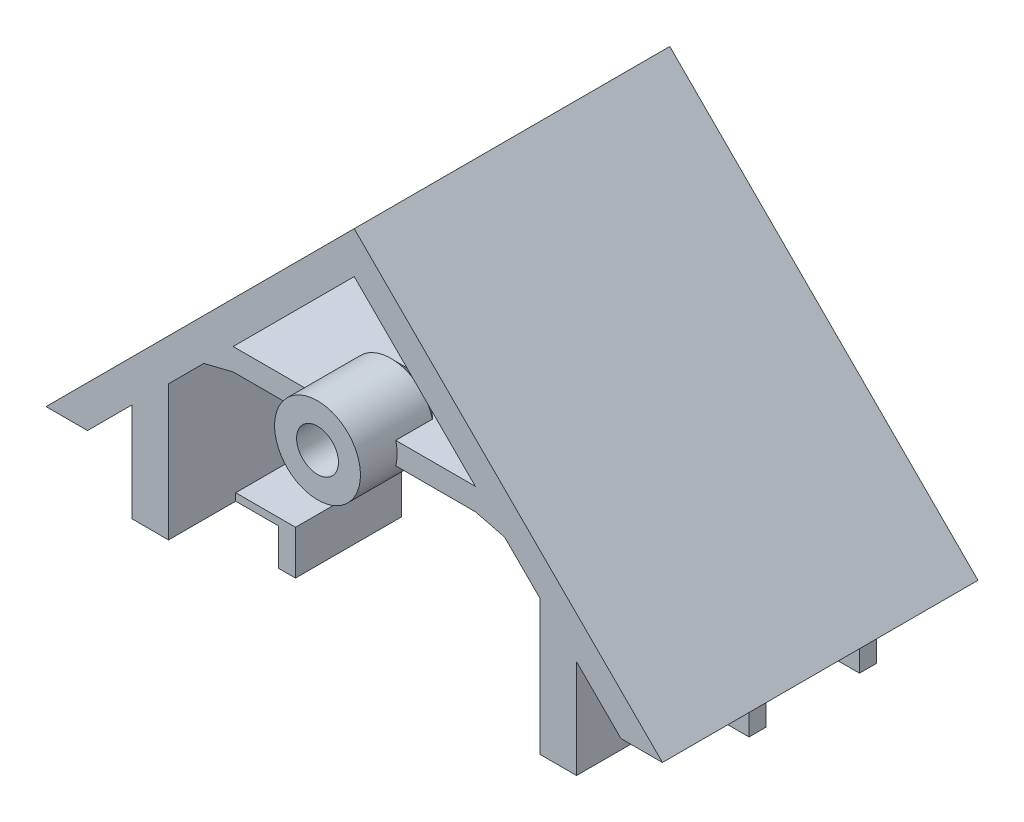
SolidWorks part; units mm, degrees
ref_plane "Front Plane" through (0, 0, 0) normal (0, 0, 1) x (1, 0, 0)
ref_plane "Top Plane" through (0, 0, 0) normal (0, 1, 0) x (1, 0, 0)
ref_plane "Right Plane" through (0, 0, 0) normal (1, 0, 0) x (0, 0, -1)
sketch "Sketch1" plane through (0, 0, 0) normal (0, 0, 1) x (1, 0, 0)
  line L1 (0, 0) -> (-42, -42)
  line L2 (0, -1000.3549) -> (0, 48999.6451) construction
  line L3 (-32.3431, -38) -> (-20.5, -26.1569)
  line L4 (32.3431, -38) -> (20.5, -26.1569)
  line L5 (0, 0) -> (42, -42)
  line L7 (-42, -42) -> (-16.5, -42) construction
  line L8 (-32.3431, -38) -> (-20.5, -38) construction
  line L9 (-34, -34) -> (34, -34) construction
  line L10 (-16.5, -42) -> (-16.5, -25.1569) construction
  line L11 (16.5, -42) -> (16.5, -25.1569) construction
  line L12 (16.5, -42) -> (42, -42) construction
  line L13 (20.5, -38) -> (32.3431, -38) construction
  line L14 (-20.5, -38) -> (-20.5, -26.1569) construction
  line L15 (20.5, -38) -> (20.5, -26.1569) construction
  line L16 (-16.5, -22.1569) -> (0, -5.6569)
  line L17 (16.5, -22.1569) -> (0, -5.6569)
  line L18 (16.5, -22.1569) -> (-16.5, -22.1569)
  line L19 (16.5, -25.1569) -> (-16.5, -25.1569)
  line L20 (-32.3431, -38) -> (-36.3431, -42)
  line L21 (-16.5, -25.1569) -> (-20.5, -26.1569)
  line L22 (16.5, -25.1569) -> (20.5, -26.1569)
  line L23 (32.3431, -38) -> (36.3431, -42)
  line L24 (-36.3431, -42) -> (-42, -42)
  line L25 (36.3431, -42) -> (42, -42)
  point P21 (0, -25.1569)
  dimension "D1" = 90
  dimension "D2" = 4
  dimension "D3" = 4
  dimension "D4" = 68
  dimension "D5" = 8
  dimension "D6" = 33
  dimension "D7" = 4
  dimension "D8" = 3
extrude "Boss-Extrude1" add sketch "Sketch1" along normal mid plane 43
sketch "Sketch11" plane through (0, 0, 21.5) normal (0, 0, 1) x (1, 0, 0)
  line L0 (0, -22.1569) -> (0, -25.1569) construction
  line L1 (-16.5, -22.1569) -> (16.5, -22.1569) construction
  line L2 (-16.5, -25.1569) -> (16.5, -25.1569) construction
  circle A0 centre (0, -23.6569) radius 5.85
  circle A1 centre (0, -23.6569) radius 2.85 construction
  point P8 (0, -23.6569)
  dimension "D1" = 5.7
  dimension "D2" = 3
extrude "Boss-Extrude7" add sketch "Sketch11" against normal blind 10 from offset 5
sketch "Sketch12" plane through (0, 0, 26.5) normal (0, 0, -1) x (-1, 0, 0)
  circle A0 centre (0, -23.6569) radius 2.85
  dimension "D1" = 5.7
extrude "Cut-Extrude3" cut sketch "Sketch12" along normal offset from surface (9 mm away) 1 up to face at (0, -19.9819, 16.5)
ref_plane "AurigaTop" through (0, -49.4896, 0) normal (0, 1, 0) x (1, 0, 0)
sketch "Sketch14" plane through (0, -49.4896, 0) normal (0, 1, 0) x (1, 0, 0)
  line L0 (-42, -21.5) -> (-42, 21.5) construction
  line L1 (-30.3, 21.5) -> (-25.3, 21.5)
  line L2 (-30.3, 21.5) -> (-30.3, -21.5)
  line L3 (-30.3, -21.5) -> (-25.3, -21.5)
  line L4 (-25.3, 21.5) -> (-25.3, -21.5)
  line L5 (-34.8, -15.55) -> (-34.8, -42.5) construction
  line L6 (0, 21.5) -> (-42, 21.5) construction
  point P6 (-42, 0)
  point P7 (-30.3, 0)
  point P8 (-27.8, 21.5)
  dimension "D1" = 5
  dimension "D3" = 7
extrude "Boss-Extrude8" add sketch "Sketch14" along normal up to next from offset 0.1
sketch "Sketch17" plane through (0, -49.3896, 0) normal (0, -1, 0) x (1, 0, 0)
  line L0 (-30.3, 21.5) -> (-25.3, 21.5) construction
  line L5 (-32.8, 0.5) -> (-19.75, 0.5) construction
  line L6 (-32.75, -14.55) -> (-19.75, -14.55) construction
  line L7 (-32.8, -14.55) -> (-22.8, -14.55) construction
  line L8 (-32.8, -14.55) -> (-32.8, -17.45) construction
  line L9 (-32.8, -17.45) -> (-22.8, -17.45) construction
  line L10 (-22.8, -14.55) -> (-22.8, -17.45) construction
  line L11 (-32.75, -17.45) -> (-19.75, -17.45) construction
  line L12 (-17.15, 12.35) -> (-17.15, -2.1)
  line L17 (-32.5, -14.85) -> (-32.5, -17.15)
  line L18 (-32.5, -17.15) -> (-23.1, -17.15)
  line L19 (-23.1, -14.85) -> (-23.1, -17.15)
  line L20 (-32.5, -14.85) -> (-23.1, -14.85)
  line L21 (-32.75, 0.5) -> (-19.75, 0.5) construction
  line L22 (-19.75, 0.5) -> (-19.75, 12.65) construction
  line L23 (-19.75, 12.65) -> (-16.85, 12.65) construction
  line L24 (-16.85, 12.65) -> (-16.85, -2.4) construction
  line L25 (-16.85, -2.4) -> (-32.8, -2.4) construction
  line L26 (-32.75, -2.4) -> (-19.75, -2.4) construction
  line L27 (-32.8, -2.4) -> (-32.8, 0.5) construction
  line L28 (-17.15, -2.1) -> (-32.5, -2.1)
  line L29 (-32.5, -2.1) -> (-32.5, 0.2)
  line L30 (-32.5, 0.2) -> (-19.45, 0.2)
  line L31 (-19.45, 0.2) -> (-19.45, 12.35)
  line L32 (-19.45, 12.35) -> (-17.15, 12.35)
  point P3 (-27.8, 21.5)
  point P20 (-27.8, -14.55)
  dimension "D1" = 10
  dimension "D3" = 0.3
extrude "Boss-Extrude10" add sketch "Sketch17" along normal blind 5
sketch "Sketch18" plane through (0, -49.3896, 0) normal (0, 1, 0) x (1, 0, 0)
  line L2 (-17.15, -12.35) -> (-25.3, -12.35)
  line L3 (-17.15, -12.35) -> (-17.15, 2.1)
  line L4 (-17.15, 2.1) -> (-25.3, 2.1)
  line L5 (-25.3, -12.35) -> (-25.3, 2.1)
extrude "Boss-Extrude11" add sketch "Sketch18" along normal blind 1
mirror "Mirror2" about plane through (0, 0, 0) normal (1, 0, 0) of "Boss-Extrude11", "Boss-Extrude8", "Boss-Extrude10"
sketch "Sketch15" plane through (0, 0, 0) normal (1, 0, 0) x (0, 0, -1)
  line L0 (-16.5, -17.8069) -> (-10.65, -23.6569)
  line L1 (-10.65, -23.6569) -> (-16.5, -23.6569)
  line L2 (-16.5, -23.6569) -> (-16.5, -17.8069)
  line L3 (-21.5, -22.1569) -> (-21.5, -25.1569) construction
  point P8 (-21.5, -23.6569)
  dimension "D1" = 45
revolve "Revolve1" add sketch "Sketch15" angle 360 about L1
sketch "Sketch10" plane through (0, -25.1569, 0) normal (0, -1, 0) x (1, 0, 0)
  line L0 (0, 14.4) -> (0, -14.4) construction
  line L2 (-16.5, 21.5) -> (-5.6544, 21.5) construction
  circle A0 centre (0, 14.4) radius 2.1
  circle A1 centre (0, -14.4) radius 2.1
  dimension "D1" = 4.2
  dimension "D2" = 5
extrude "Cut-Extrude2" [suppressed] cut sketch "Sketch10" against normal blind 10
sketch "Sketch5" [suppressed] plane through (0, 0, 21.5) normal (0, 0, 1) x (1, 0, 0)
  line L1 (0, 0) -> (-42, -42) construction
  line L2 (-35.2, -35.2) -> (-32.2, -35.2)
  line L3 (-32.2, -35.2) -> (-32.2, -42)
  line L5 (-32.2, -42) -> (-40.2, -42)
  line L6 (-40.2, -42) -> (-40.2, -40.2)
  line L7 (-40.2, -40.2) -> (-35.2, -35.2)
  line L9 (-42, -42) -> (-36.3431, -42) construction
  line L10 (-40.4, 30.0104) -> (-40.4, -66.9896) construction
  dimension "D1" = 8
  dimension "D2" = 3
  dimension "D3" = 0.2
extrude "Boss-Extrude4" [suppressed] add sketch "Sketch5" along normal up to surface (24.9 mm away)
sketch "Sketch8" [suppressed] plane through (0, 0, 20) normal (0, 0, -1) x (-1, 0, 0)
  line L3 (32.2, -42) -> (36.3431, -42)
  line L4 (36.3431, -42) -> (32.2, -37.8569)
  line L5 (32.2, -37.8569) -> (32.2, -42)
  line L6 (32.2, -42) -> (36.3431, -42)
  line L7 (36.3431, -42) -> (32.2, -37.8569)
  line L8 (32.2, -37.8569) -> (32.2, -42)
  dimension "D1" = 0
extrude "Boss-Extrude6" [suppressed] add sketch "Sketch8" along normal blind 5.5
sketch "Sketch6" [suppressed] plane through (0, 0, 44.9) normal (0, 0, 1) x (1, 0, 0)
  line L0 (-40.2, -40.2) -> (-40.2, -42) construction
  line L1 (-32.2, -42) -> (-40.2, -42)
  line L2 (-32.2, -42) -> (-32.2, -32)
  line L3 (-32.2, -32) -> (-40.2, -32)
  line L4 (-40.2, -42) -> (-40.2, -32)
  line L5 (-32.2, -42) -> (-32.2, -35.2) construction
  line L6 (-40.2, -42) -> (-32.2, -42) construction
  dimension "D1" = 10
  dimension "D2" = 0
extrude "Boss-Extrude5" [suppressed] add sketch "Sketch6" along normal blind 16
sketch "Sketch7" [suppressed] plane through (-32.2, 0, 0) normal (1, 0, 0) x (0, 0, -1)
  line L0 (-60.9, -32) -> (-44.9, -32) construction
  line L1 (-60.9, -42) -> (-60.9, -32) construction
  circle A0 centre (-52.9, -37) radius 2.1
  point P5 (-52.9, -32)
  point P8 (-60.9, -37)
  dimension "D1" = 4.2
extrude "Cut-Extrude1" [suppressed] cut sketch "Sketch7" against normal through all
mirror "Mirror1" [suppressed] about plane through (0, 0, 0) normal (1, 0, 0)
equation "\"width\"= 24"
equation "\"thk\"= 3"
equation "\"holesize\"= 4.2"
equation "\"holedistance\"= ( 20 + 12 ) / 2"
equation "\"threaded_hole\"= 3.9"
equation "\"fillet_radius\"= 2"
equation "\"ground_clearance\"= 25"
equation "\"tire_thk\"= 3"
equation "\"innerwheel_diam\" = \"wheel_diam\"-2*\"tire_thk\""
equation "\"innerwheel_thk\"= 8"
equation "\"wheel_diam\"= 2*(\"width\"/2+\"ground_clearance\")"
equation "\"coloursensor_holesize\"= 2.65"
equation "\"hole_to_edge\" = 4"
equation "\"D1@Sketch7\"=\"holesize\""
equation "\"D7@Sketch1\"=\"D2@Sketch1\""
equation "\"D1@Sketch10\"=\"holesize\""
equation "\"M4_insert_diam\"= 5.7"
equation "\"D1@Sketch11\"=\"M4_insert_diam\""
equation "\"D1@Sketch12\"=\"M4_insert_diam\""
equation "\"D2@Sketch17\"=\"D3@Sketch17\""
